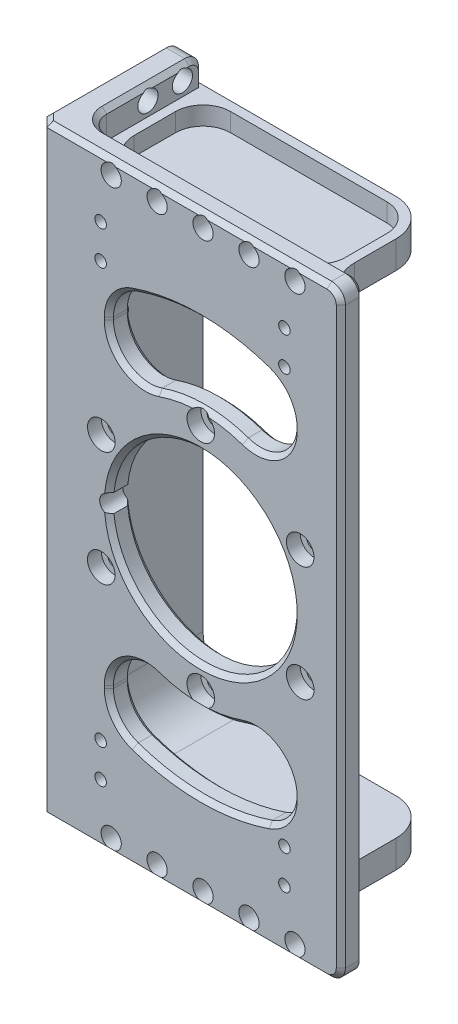
SolidWorks part; units mm, degrees
material "6061 合金"
ref_plane "前视基准面" through (0, 0, 0) normal (0, 0, 1) x (1, 0, 0)
ref_plane "上视基准面" through (0, 0, 0) normal (0, 1, 0) x (1, 0, 0)
ref_plane "右视基准面" through (0, 0, 0) normal (1, 0, 0) x (0, 0, -1)
sketch "草图1" plane through (0, 0, 0) normal (0, 0, 1) x (1, 0, 0)
  line L0 (-237.1759, 120) -> (-237.1759, 1) construction
  line L1 (-237.1759, 60.5) -> (-177.1759, 60.5) construction
  line L2 (812.8241, 60.5) -> (-387.1759, 60.5) construction
  line L3 (-165.4601, -5) -> (-232.1759, -5) construction
  line L4 (-237.1759, 126) -> (-177.1759, 126)
  line L5 (-237.1759, 126) -> (-237.1759, -5)
  line L6 (-237.1759, -5) -> (-177.1759, -5)
  line L7 (-177.1759, 126) -> (-177.1759, -5)
extrude "凸台-拉伸1" add sketch "草图1" along normal blind 5
sketch "草图2" plane through (-237.1759, 0, 0) normal (-1, 0, 0) x (0, 0, 1)
  line L0 (-235, 126) -> (-5, 126) construction
  line L1 (5, -5) -> (-25, -5)
  line L2 (5, -5) -> (5, 126)
  line L3 (5, 126) -> (-25, 126)
  line L4 (-25, -5) -> (-25, 126)
extrude "凸台-拉伸2" add sketch "草图2" along normal blind 6
sketch "草图3" plane through (0, 0, 5) normal (0, 0, 1) x (1, 0, 0)
  line L2 (-236.1759, 60.5) -> (-179.1759, 60.5) construction
  circle A2 centre (-207.6759, 60.5) radius 28.5 construction
  circle A3 centre (-207.6759, 60.5) radius 25 construction
  circle A4 centre (-207.6759, 60.5) radius 20
  dimension "D1" = 5
extrude "切除-拉伸1" cut sketch "草图3" against normal blind 10
sketch "草图4" plane through (0, 0, 5) normal (0, 0, 1) x (1, 0, 0)
  line L4 (-177.1759, 126) -> (-243.1759, 126)
  line L5 (-243.1759, 126) -> (-243.1759, -5)
  line L6 (-243.1759, -5) -> (-177.1759, -5)
  line L7 (-177.1759, -5) -> (-177.1759, 126)
  line L8 (-177.1759, 126) -> (-243.1759, 126)
  line L9 (-243.1759, 126) -> (-243.1759, -5)
  line L10 (-243.1759, -5) -> (-177.1759, -5)
  line L11 (-177.1759, -5) -> (-177.1759, 126)
  circle A0 centre (-207.6759, 60.5) radius 20 construction
  circle A1 centre (-207.6759, 60.5) radius 20
  dimension "D1" = 0
chamfer "倒角1" distance 2 angle 45 1 edges at (-243.1759, 60.5, 5)
fillet "圆角1" radius 3 4 edges at (-240.1759, 126, -25) (-177.1759, 126, 2.5) (-177.1759, -5, 2.5) (-240.1759, -5, -25)
sketch "草图5" plane through (0, 0, 5) normal (0, 0, 1) x (1, 0, 0)
  circle A0 centre (-207.6759, 60.5) radius 25 construction
  point P3 (-207.6759, 85.5)
  point P4 (-186.0252, 73)
  point P7 (-186.0252, 48)
  point P8 (-207.6759, 35.5)
  point P9 (-229.3265, 48)
  point P10 (-229.3265, 73)
  point P11 (-207.6759, 60.5)
  dimension "D1" = 6
sketch "草图13" plane through (0, 0, 5) normal (0, 0, 1) x (1, 0, 0)
  circle A0 centre (-207.6759, 85.5) radius 1.6
  circle A1 centre (-229.3265, 73) radius 1.6
  circle A2 centre (-186.0252, 73) radius 1.6
  circle A3 centre (-186.0252, 48) radius 1.6
  circle A4 centre (-207.6759, 35.5) radius 1.6
  circle A5 centre (-229.3265, 48) radius 1.6
extrude "切除-拉伸2" cut sketch "草图13" against normal blind 6
sketch "草图14" plane through (0, 0, 5) normal (0, 0, 1) x (1, 0, 0)
  circle A0 centre (-207.6759, 85.5) radius 3
  circle A1 centre (-186.0252, 73) radius 3
  circle A2 centre (-186.0252, 48) radius 3
  circle A3 centre (-207.6759, 35.5) radius 3
  circle A4 centre (-229.3265, 48) radius 3
  circle A5 centre (-229.3265, 73) radius 3
extrude "切除-拉伸3" cut sketch "草图14" against normal blind 3
chamfer "倒角4" distance 1 angle 45 12 edges at (-242.1759, -5, 4) (-210.6759, -5, 5) (-243.1759, -5, -9.5) (-178.0545, -4.1213, 5) (-243.1759, -4.1213, -24.1213) (-177.1759, 60.5, 5) (-243.1759, 60.5, -25) (-178.0545, 125.1213, 5) (-243.1759, 125.1213, -24.1213) (-210.6759, 126, 5) (-242.1759, 126, 4) (-243.1759, 126, -9.5)
sketch "草图15" plane through (0, 0, 0) normal (0, -1, 0) x (1, 0, 0)
  line L0 (-11.5, -120) -> (-5.5, -120) construction
  line L1 (-11.5, -191) -> (-11.5, -49) construction
  line L2 (-5.5, -108) -> (-5.5, -132) construction
  line L3 (-8.5, -100) -> (-8.5, -140) construction
  line L4 (-8.5, -80) -> (-8.5, -160) construction
  line L5 (-8.5, -60) -> (-8.5, -180) construction
  point P9 (-8.5, -120)
  point P13 (-8.5, -120)
  point P16 (-8.5, -120)
sketch "草图16" plane through (0, 0, 0) normal (0, 0, -1) x (-1, 0, 0)
  line L5 (237.1759, 126) -> (237.1759, 120) construction
  line L6 (237.1759, 123) -> (237.1759, -2) construction
  line L8 (237.1759, 120) -> (187.1759, 120)
  line L9 (237.1759, 120) -> (237.1759, 114)
  line L10 (237.1759, 114) -> (187.1759, 114)
  line L11 (187.1759, 120) -> (187.1759, 114)
extrude "凸台-拉伸4" add sketch "草图16" along normal up to surface (25 mm away) up to face at (-239.6759, 60.5, -25)
ref_plane "基准面1" through (0, 60.5, 0) normal (0, -1, 0) x (-1, 0, 0)
mirror "镜向1" about plane through (0, 60.5, 0) normal (0, -1, 0) of "凸台-拉伸4"
fillet "圆角3" radius 4 2 edges at (-237.1759, -2, 0) (-237.1759, 123, 0)
fillet "圆角4" radius 10 2 edges at (-237.1759, 114, -12.5) (-237.1759, 7, -12.5)
fillet "圆角5" radius 8 4 edges at (-187.1759, 117, 0) (-187.1759, 117, -25) (-187.1759, 4, 0) (-187.1759, 4, -25)
sketch "草图17" plane through (0, 120, 0) normal (0, 1, 0) x (1, 0, 0)
  line L4 (-235.1759, 4) -> (-235.1759, 2)
  line L5 (-235.1759, 2) -> (-233.1759, 2)
  line L8 (-189.1759, 8) -> (-189.1759, 17)
  line L9 (-195.1759, 23) -> (-235.1759, 23)
  line L10 (-235.1759, 23) -> (-235.1759, 4)
  line L11 (-233.1759, 2) -> (-187.1759, 2)
  line L12 (-189.1759, 8) -> (-189.1759, 17)
  line L13 (-195.1759, 23) -> (-235.1759, 23)
  line L14 (-235.1759, 23) -> (-235.1759, 4)
  line L15 (-233.1759, 2) -> (-187.1759, 2)
  arc A6 (-189.1759, 17) -> (-195.1759, 23) centre (-195.1759, 17) ccw
  arc A7 (-235.1759, 4) -> (-233.1759, 2) centre (-233.1759, 4) ccw
  arc A8 (-189.1759, 8) -> (-187.1759, 2) centre (-179.1759, 8) ccw
  arc A9 (-189.1759, 17) -> (-195.1759, 23) centre (-195.1759, 17) ccw
  arc A11 (-189.1759, 8) -> (-187.1759, 2) centre (-179.1759, 8) ccw
  dimension "D1" = 2
extrude "切除-拉伸4" cut sketch "草图17" against normal blind 4
mirror "镜向2" about plane through (0, 60.5, 0) normal (0, -1, 0) of "切除-拉伸4"
fillet "圆角6" radius 6 6 edges at (-187.1759, 118, -2) (-235.1759, 118, -23) (-235.1759, 118, -2) (-235.1759, 3, -23) (-187.1759, 3, -2) (-235.1759, 3, -2)
sketch "草图19" plane through (0, 0, 5) normal (0, 0, 1) x (1, 0, 0)
  line L0 (-243.1759, -5) -> (-237.1759, -5) construction
  line L1 (-243.1759, -5) -> (-177.1759, -5) construction
  line L2 (-237.1759, -5) -> (-177.1759, -5) construction
  line L3 (-207.1759, -5) -> (-207.1759, 1) construction
  line L4 (-217.1759, -2) -> (-197.1759, -2)
  line L5 (-227.1759, -2) -> (-187.1759, -2)
  circle A0 centre (-227.1759, -2) radius 2.2
  circle A1 centre (-217.1759, -2) radius 2.2
  circle A2 centre (-207.1759, -2) radius 2.2
  circle A3 centre (-197.1759, -2) radius 2.2
  circle A4 centre (-187.1759, -2) radius 2.2
  point P13 (-207.1759, -2)
  point P15 (-207.1759, -2)
extrude "切除-拉伸5" cut sketch "草图19" against normal blind 18
mirror "镜向3" about plane through (0, 60.5, 0) normal (0, -1, 0) of "切除-拉伸5"
sketch "草图20" plane through (-243.1759, 0, 0) normal (-1, 0, 0) x (0, 0, 1)
  line L0 (5, -5) -> (-1, -5) construction
  line L1 (5, -5) -> (5, 126) construction
  line L2 (4, -5) -> (2.5858, -5) construction
  line L3 (-1, -5) -> (-25, -5) construction
  line L4 (-5, -5) -> (-235, -5) construction
  line L5 (-13, -5) -> (-13, 1) construction
  line L6 (-20.5, -2) -> (-5.5, -2) construction
  circle A0 centre (-20.5, -2) radius 2.2
  circle A1 centre (-13, -2) radius 2.2
  point P15 (-13, -2)
extrude "切除-拉伸6" cut sketch "草图20" against normal blind 18
mirror "镜向4" about plane through (0, 60.5, 0) normal (0, -1, 0) of "切除-拉伸6"
sketch "草图21" plane through (0, 0, 5) normal (0, 0, 1) x (1, 0, 0)
  line L0 (-207.6759, 60.5) -> (-209.4659, 60.5)
  line L1 (-14.3, 60.5) -> (14.3, 60.5) construction
  line L2 (-209.4659, 60.5) -> (-209.4659, 64.19)
  line L4 (-229.4659, 113.065) -> (-189.4659, 113.065)
  line L5 (-229.4659, 113.065) -> (-229.4659, 15.315)
  line L6 (-229.4659, 15.315) -> (-189.4659, 15.315)
  line L7 (-189.4659, 113.065) -> (-189.4659, 15.315)
  line L8 (-229.4659, 113.065) -> (-189.4659, 15.315) construction
  line L9 (-229.4659, 15.315) -> (-189.4659, 113.065) construction
hole_wizard "M3 螺纹孔1" positions "草图22" profile "草图23" tap size "M3" standard "GB"
sketch "草图22" plane through (0, 0, 5) normal (0, 0, 1) x (1, 0, 0)
  point P0 (-229.4659, 113.065)
  point P3 (-189.4659, 113.065)
  point P6 (-189.4659, 15.315)
  point P9 (-229.4659, 15.315)
sketch "草图23" plane through (-229.4659, 113.065, 5) normal (1, 0, 0) x (0, -1, 0)
  line L0 (0, 0) -> (0, 8.2511)
  line L1 (0, 8.2511) -> (1.25, 7.5)
  line L2 (1.25, 7.5) -> (1.25, 0)
  line L5 (1.25, 0) -> (0, 0)
  line L10 (0, 8.2511) -> (-1.25, 7.5) construction
  line L11 (0, -6.35) -> (0, 107.95) construction
  dimension "螺纹孔钻头直径" = 2.5
  dimension "螺纹孔钻头深度" = 7.5
  dimension "导头角度" = 118
cosmetic thread "孔螺蚊线1" parameters "D1"=6, "D2"=3
cosmetic thread "孔螺蚊线2" parameters "D1"=6, "D2"=3
cosmetic thread "孔螺蚊线3" parameters "D1"=6, "D2"=3
cosmetic thread "孔螺蚊线4" parameters "D1"=6, "D2"=3
mirror "镜向5" about plane through (0, 60.5, 0) normal (0, -1, 0) of "M3 螺纹孔1"
cosmetic thread "孔螺蚊线5" parameters "D1"=6, "D2"=3
cosmetic thread "孔螺蚊线6" parameters "D1"=6, "D2"=3
cosmetic thread "孔螺蚊线7" parameters "D1"=6, "D2"=3
cosmetic thread "孔螺蚊线8" parameters "D1"=6, "D2"=3
sketch "草图24" plane through (-243.1759, 0, 0) normal (-1, 0, 0) x (0, 0, 1)
  line L0 (5, 60.5) -> (-7.12, 60.5)
  line L3 (-14.3, 60.5) -> (14.3, 60.5) construction
  line L4 (-7.12, 60.5) -> (-7.12, 35.2)
  line L5 (-7.12, 60.5) -> (-7.12, 85.8)
hole_wizard "M4 螺纹孔1" positions "草图25" profile "草图26" tap size "M4" standard "GB"
sketch "草图25" plane through (-243.1759, 0, 0) normal (-1, 0, 0) x (0, 0, 1)
  point P0 (-7.12, 85.8)
  point P3 (-7.12, 35.2)
sketch "草图26" plane through (-243.1759, 85.8, -7.12) normal (0, 1, 0) x (0, 0, 1)
  line L0 (0, 0) -> (0, 11.0914)
  line L1 (0, 11.0914) -> (1.65, 10.1)
  line L2 (1.65, 10.1) -> (1.65, 0)
  line L5 (1.65, 0) -> (0, 0)
  line L10 (0, 11.0914) -> (-1.65, 10.1) construction
  line L11 (0, -6.35) -> (0, 107.95) construction
  dimension "螺纹孔钻头直径" = 3.3
  dimension "螺纹孔钻头深度" = 10.1
  dimension "导头角度" = 118
cosmetic thread "孔螺蚊线9" parameters "D1"=8, "D2"=4
cosmetic thread "孔螺蚊线10" parameters "D1"=8, "D2"=4
sketch "草图27" plane through (0, 0, 0) normal (0, 0, -1) x (-1, 0, 0)
  line L0 (207.6759, 105.5) -> (207.6759, 89) construction
  line L1 (187.6759, 100.8113) -> (187.6759, 80.8039)
  line L2 (227.6759, 100.8113) -> (227.6759, 80.8039)
  line L3 (227.6759, 60.5) -> (227.6759, -966.5522) construction
  line L4 (207.6759, 60.5) -> (207.6759, -966.5522) construction
  line L5 (187.6759, 60.5) -> (187.6759, -966.5522) construction
  line L6 (187.6759, 40.1961) -> (187.6759, 20.1887)
  line L7 (207.6759, 32) -> (207.6759, 15.5) construction
  line L8 (227.6759, 40.1961) -> (227.6759, 20.1887)
  arc A0 (187.6759, 40.1961) -> (227.6759, 40.1961) centre (207.6759, 60.5) ccw
  arc A1 (187.6759, 20.1887) -> (227.6759, 20.1887) centre (207.6759, 60.5) ccw
  arc A2 (227.6759, 80.8039) -> (187.6759, 80.8039) centre (207.6759, 60.5) ccw
  arc A3 (227.6759, 100.8113) -> (187.6759, 100.8113) centre (207.6759, 60.5) ccw
  dimension "D1" = 20
  dimension "D2" = 20
extrude "切除-拉伸7" cut sketch "草图27" against normal blind 10
fillet "圆角7" radius 8 8 edges at (-187.6759, 20.1887, 2.5) (-227.6759, 40.1961, 2.5) (-227.6759, 20.1887, 2.5) (-187.6759, 40.1961, 2.5) (-187.6759, 80.8039, 2.5) (-227.6759, 100.8113, 2.5) (-227.6759, 80.8039, 2.5) (-187.6759, 100.8113, 2.5)
chamfer "倒角5" distance 1 angle 45 34 edges at (-187.6759, 60.5, 0) (-187.6759, 60.5, 5) (-207.6759, 105.5, 0) (-189.166, 100.1499, 0) (-226.1857, 100.1499, 0) (-187.6759, 95.2355, 0) (-227.6759, 95.2355, 0) (-191.0413, 88.4502, 0) (-224.3105, 88.4502, 0) (-207.6759, 89, 0) (-207.6759, 89, 5) (-191.0413, 88.4502, 5) (-224.3105, 88.4502, 5) (-187.6759, 95.2355, 5) (-227.6759, 95.2355, 5) (-189.166, 100.1499, 5) (-226.1857, 100.1499, 5) (-207.6759, 105.5, 5) (-207.6759, 32, 0) (-191.0413, 32.5498, 0) (-224.3105, 32.5498, 0) (-187.6759, 25.7645, 0) (-227.6759, 25.7645, 0) (-189.166, 20.8501, 0) (-226.1857, 20.8501, 0) (-207.6759, 15.5, 0) (-207.6759, 32, 5) (-224.3105, 32.5498, 5) (-191.0413, 32.5498, 5) (-227.6759, 25.7645, 5) (-187.6759, 25.7645, 5) (-226.1857, 20.8501, 5) (-189.166, 20.8501, 5) (-207.6759, 15.5, 5)
chamfer "倒角6" distance 1 angle 45 13 edges at (-237.1759, -0.5, -25) (-237.1759, 121.5, -25) (-237.1759, -4.1213, -24.1213) (-237.1759, 125.1213, -24.1213) (-237.1759, -5, -13) (-237.1759, 126, -13) (-236.0043, -5, -1.1716) (-236.0043, 126, -1.1716) (-206.6759, -5, 0) (-206.6759, 126, 0) (-178.0545, -4.1213, 0) (-178.0545, 125.1213, 0) (-177.1759, 60.5, 0)
sketch "草图29" plane through (0, 0, 5) normal (0, 0, 1) x (1, 0, 0)
  circle A0 centre (-227.6759, 60.5) radius 2
  dimension "D1" = 4
extrude "切除-拉伸8" cut sketch "草图29" against normal blind 10
sketch "草图30" plane through (0, 0, 0) normal (0, 0, -1) x (-1, 0, 0)
  circle A0 centre (214.1463, 36.3519) radius 1.5
  dimension "D1" = 3
extrude "切除-拉伸9" cut sketch "草图30" against normal blind 3
pattern_circular "阵列(圆周)1" count 6 over 360 about axis through (-207.6759, 60.5, 0) along (0, 0, 1) of "切除-拉伸9"
